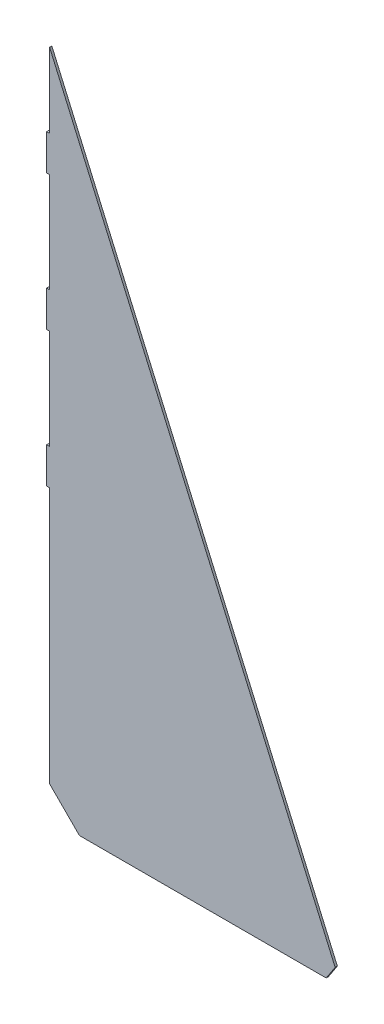
SolidWorks part; units mm, degrees
ref_plane "Front Plane" through (0, 0, 0) normal (0, 0, 1) x (1, 0, 0)
ref_plane "Top Plane" through (0, 0, 0) normal (0, 1, 0) x (1, 0, 0)
ref_plane "Right Plane" through (0, 0, 0) normal (1, 0, 0) x (0, 0, -1)
sketch "Sketch1" plane through (0, 0, 0) normal (0, 0, 1) x (1, 0, 0)
  line L0 (0, 0) -> (0, 297.8632)
  line L1 (0, 297.8632) -> (191.5032, -140.8352)
  line L2 (185.5039, -150) -> (20, -150)
  line L3 (0, -130) -> (0, 0)
  line L4 (20, -150) -> (0, -130)
  line L5 (191.5032, -140.8352) -> (185.5039, -150)
  point P4 (195.5039, -150)
  point P5 (0, -150)
  dimension "D2" = 150
extrude "Boss-Extrude1" add sketch "Sketch1" along normal blind 1.5
sketch "Sketch7" plane through (0, 0, 0) normal (-1, 0, 0) x (0, 0, 1)
  line L0 (0, 247.8632) -> (1.5, 247.8632)
  line L1 (0, 297.8632) -> (0, -130) construction
  line L2 (1.5, 297.8632) -> (1.5, -130) construction
  line L3 (1.5, 247.8632) -> (1.5, 223.8632)
  line L4 (1.5, 223.8632) -> (0, 223.8632)
  line L5 (0, 223.8632) -> (0, 247.8632)
  line L6 (1.5, 297.8632) -> (0, 297.8632) construction
  line L7 (-31.75, 1.9834) -> (33.25, 1.9834) construction
  line L8 (0, 156.9834) -> (1.5, 156.9834)
  line L9 (0, 156.9834) -> (0, 132.9834)
  line L10 (0, 132.9834) -> (1.5, 132.9834)
  line L11 (1.5, 156.9834) -> (1.5, 132.9834)
  line L12 (0, 41.9834) -> (1.5, 41.9834)
  line L13 (0, 41.9834) -> (0, 65.9834)
  line L14 (0, 65.9834) -> (1.5, 65.9834)
  line L15 (1.5, 41.9834) -> (1.5, 65.9834)
  dimension "D1" = 24
  dimension "D2" = 50
  dimension "D3" = 24
  dimension "D4" = 24
  dimension "D5" = 40
  dimension "D6" = 67
extrude "Boss-Extrude3" add sketch "Sketch7" along normal blind 2
